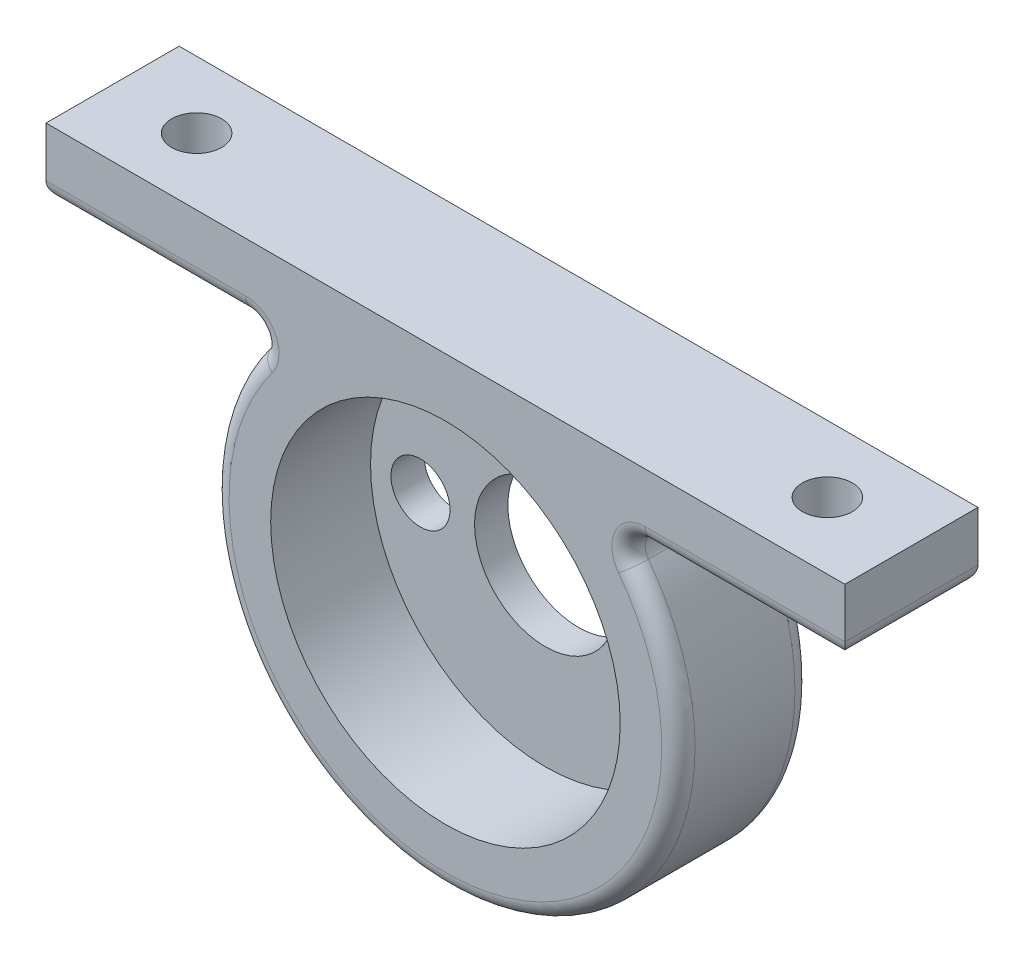
SolidWorks part; units mm, degrees
material "ABS"
ref_plane "Alzado" through (0, 0, 0) normal (0, 0, 1) x (1, 0, 0)
ref_plane "Planta" through (0, 0, 0) normal (0, 1, 0) x (1, 0, 0)
ref_plane "Vista lateral" through (0, 0, 0) normal (1, 0, 0) x (0, 0, -1)
sketch "Croquis1" plane through (0, 0, 0) normal (0, 0, 1) x (1, 0, 0)
  line L0 (0, 14) -> (24, 14)
  line L1 (0, 14) -> (-24, 14)
  line L2 (-24, 14) -> (-24, 10)
  line L3 (-24, 10) -> (-9.798, 10)
  line L4 (24, 14) -> (24, 10)
  line L5 (24, 10) -> (9.798, 10)
  arc A1 (-9.798, 10) -> (9.798, 10) centre (0, 0) ccw
  dimension "D1" = 14
  dimension "D2" = 14
  dimension "D3" = 48
  dimension "D5" = 4
  dimension "D6" = 4
  dimension "D7" = 24
extrude "Saliente-Extruir1" add sketch "Croquis1" along normal blind 8
fillet "Redondeo1" radius 1 10 edges at (-16.899, 10, 8) (-16.899, 10, 0) (16.899, 10, 8) (16.899, 10, 0) (-9.798, 10, 4) (0, -14, 8) (9.798, 10, 4) (0, -14, 0) (24, 10, 4) (-24, 10, 4)
sketch "Croquis2" plane through (0, 10, 0) normal (0, -1, 0) x (1, 0, 0)
  line L0 (23, 1) -> (23, 7) construction
  line L2 (12, 1) -> (23, 1) construction
  line L4 (-23, 1) -> (-12, 1) construction
  line L5 (-23, 7) -> (-23, 1) construction
  circle A0 centre (-18.9495, 4) radius 1.5
  circle A1 centre (18.9495, 4) radius 1.5
  dimension "D1" = 3
  dimension "D2" = 3
  dimension "D3" = 4.0505
  dimension "D4" = 3
  dimension "D5" = 3
  dimension "D6" = 4.0505
extrude "Cortar-Extruir1" cut sketch "Croquis2" against normal through all
sketch "Croquis3" plane through (0, 0, 8) normal (0, 0, 1) x (1, 0, 0)
  circle A0 centre (0, 0) radius 10.5
  dimension "D1" = 21
extrude "Cortar-Extruir2" cut sketch "Croquis3" against normal blind 6
sketch "Croquis4" plane through (0, 0, 0) normal (0, 0, -1) x (-1, 0, 0)
  line L0 (-24, 14) -> (24, 14) construction
  circle A0 centre (0, 0) radius 4.25
  circle A1 centre (7.5, 0) radius 1.775
  circle A2 centre (-7.5, 0) radius 1.775
  dimension "D1" = 8.5
  dimension "D2" = 7.5
  dimension "D3" = 7.5
  dimension "D4" = 3.55
  dimension "D5" = 3.55
  dimension "D6" = 14
  dimension "D7" = 14
extrude "Cortar-Extruir3" cut sketch "Croquis4" against normal through all
